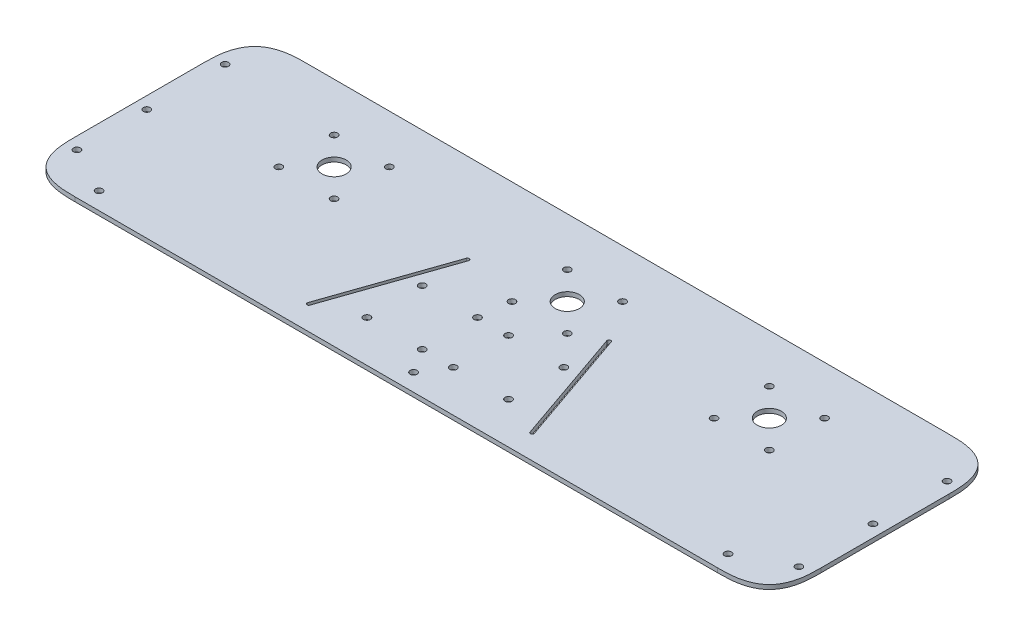
SolidWorks part; units mm, degrees
ref_plane "Front Plane" through (0, 0, 0) normal (0, 0, 1) x (1, 0, 0)
ref_plane "Top Plane" through (0, 0, 0) normal (0, 1, 0) x (1, 0, 0)
ref_plane "Right Plane" through (0, 0, 0) normal (1, 0, 0) x (0, 0, -1)
sketch "Sketch1" plane through (0, 0, 0) normal (0, 1, 0) x (1, 0, 0)
  line L1 (-103.134, 171.9149) -> (328.866, 171.9149)
  line L2 (-103.134, 171.9149) -> (-103.134, -28.0851)
  line L3 (-103.134, -28.0851) -> (328.866, -28.0851)
  line L4 (328.866, 171.9149) -> (328.866, -28.0851)
extrude "Boss-Extrude1" add sketch "Sketch1" along normal blind 2.5 contours L1 L4 L3 L2
sketch "Sketch3" plane through (0, 2.5, 0) normal (0, 1, 0) x (1, 0, 0)
  line L0 (-13.134, 71.9149) -> (-29.1359, 55.9131)
  line L1 (2.8678, 87.9167) -> (-29.1359, 87.9167)
  line L2 (2.8678, 87.9167) -> (2.8678, 55.9131)
  line L3 (2.8678, 55.9131) -> (-29.1359, 55.9131)
  line L4 (-29.1359, 87.9167) -> (-29.1359, 55.9131)
  line L5 (2.8678, 87.9167) -> (-29.1359, 55.9131) construction
  line L6 (2.8678, 55.9131) -> (-29.1359, 87.9167) construction
  line L7 (-103.134, 71.9149) -> (-13.134, 71.9149)
  line L8 (-103.134, 171.9149) -> (-103.134, -28.0851) construction
  line L9 (238.866, 71.9149) -> (238.866, 115.9149)
  line L14 (62.253, -0.3819) -> (46.2512, -16.3837)
  line L15 (238.866, 115.9149) -> (328.866, 115.9149)
  line L18 (328.866, 171.9149) -> (328.866, -28.0851) construction
  line L19 (238.866, 71.9149) -> (222.8641, 55.9131)
  line L20 (254.8678, 87.9167) -> (222.8641, 87.9167)
  line L21 (254.8678, 87.9167) -> (254.8678, 55.9131)
  line L22 (254.8678, 55.9131) -> (222.8641, 55.9131)
  line L23 (222.8641, 87.9167) -> (222.8641, 55.9131)
  line L24 (254.8678, 87.9167) -> (222.8641, 55.9131) construction
  line L25 (254.8678, 55.9131) -> (222.8641, 87.9167) construction
  line L27 (328.866, 71.9149) -> (238.866, 71.9149)
  line L28 (238.866, 115.9149) -> (238.866, 171.9149)
  line L29 (238.866, 171.9149) -> (328.866, 171.9149)
  line L30 (328.866, 115.9149) -> (328.866, 171.9149)
  line L31 (328.866, 115.9149) -> (-169.3435, 115.9149)
  line L32 (328.866, 115.9149) -> (328.866, 173.2785)
  line L33 (328.866, 173.2785) -> (-169.3435, 173.2785)
  line L34 (-169.3435, 115.9149) -> (-169.3435, 173.2785)
  line L35 (78.2549, 15.6199) -> (46.2512, 15.6199)
  line L36 (78.2549, 15.6199) -> (78.2549, -16.3837)
  line L37 (78.2549, -16.3837) -> (46.2512, -16.3837)
  line L38 (46.2512, 15.6199) -> (46.2512, -16.3837)
  line L39 (78.2549, 15.6199) -> (46.2512, -16.3837) construction
  line L40 (78.2549, -16.3837) -> (46.2512, 15.6199) construction
  circle A0 centre (-13.134, 71.9149) radius 7
  circle A1 centre (-29.1359, 55.9131) radius 2
  circle A2 centre (-29.1359, 87.9167) radius 2
  circle A3 centre (2.8678, 87.9167) radius 2
  circle A4 centre (2.8678, 55.9131) radius 2
  circle A10 centre (238.866, 71.9149) radius 7
  circle A11 centre (222.8641, 55.9131) radius 2
  circle A12 centre (222.8641, 87.9167) radius 2
  circle A13 centre (254.8678, 87.9167) radius 2
  circle A14 centre (254.8678, 55.9131) radius 2
  circle A15 centre (62.253, -0.3819) radius 7
  circle A16 centre (46.2512, -16.3837) radius 2
  circle A17 centre (46.2512, 15.6199) radius 2
  circle A18 centre (78.2549, 15.6199) radius 2
  circle A19 centre (78.2549, -16.3837) radius 2
  point P10 (328.866, 71.9149)
extrude "Cut-Extrude1" cut sketch "Sketch3" against normal blind 2.5 contours A2 | A3 | A4 | A1 | A0 | A11 | A14 | A13 | A10 | A12 | L32 L31 L34 L33
sketch "Sketch5" plane through (0, 2.5, 0) normal (0, 1, 0) x (1, 0, 0)
  line L0 (263.7413, -28.0851) -> (263.7413, -18.0851)
  line L3 (-103.134, -28.0851) -> (328.866, -28.0851) construction
  line L5 (263.7413, -18.0851) -> (328.866, -18.0851)
  line L6 (263.7413, -18.0851) -> (263.7413, -28.0851)
  line L7 (263.7413, -28.0851) -> (328.866, -28.0851)
  line L8 (328.866, -18.0851) -> (328.866, -28.0851)
  line L9 (263.7413, -18.0851) -> (-103.134, -18.0851)
  line L10 (263.7413, -18.0851) -> (263.7413, -28.0851)
  line L11 (263.7413, -28.0851) -> (-103.134, -28.0851)
  line L12 (-103.134, -18.0851) -> (-103.134, -28.0851)
  line M12 (328.866, -28.0851) -> (328.866, 115.9149)
  line M14 (-103.134, 115.9149) -> (-103.134, -28.0851)
  line M15 (-103.134, -28.0851) -> (328.866, -28.0851)
extrude "Cut-Extrude3" cut sketch "Sketch5" against normal blind 2.5 contours L0 L9 M14 M15 | L5 L0 M15 M12 region at (80.3036, 2.5, 23.0851) region at (296.3036, 2.5, 23.0851)
sketch "Sketch6" plane through (0, 2.5, 0) normal (0, 1, 0) x (1, 0, 0)
  line L0 (328.866, -18.0851) -> (-103.134, -18.0851) construction
  line L1 (112.866, -18.0851) -> (112.866, 21.9149)
  line L2 (112.866, 21.9149) -> (137.866, 21.9149)
  line L3 (112.866, 21.9149) -> (87.866, 21.9149)
  line L4 (87.866, 21.9149) -> (71.8641, 5.9131)
  line L5 (103.8678, 37.9167) -> (71.8641, 37.9167)
  line L6 (103.8678, 37.9167) -> (103.8678, 5.9131)
  line L7 (103.8678, 5.9131) -> (71.8641, 5.9131)
  line L8 (71.8641, 37.9167) -> (71.8641, 5.9131)
  line L9 (103.8678, 37.9167) -> (71.8641, 5.9131) construction
  line L10 (103.8678, 5.9131) -> (71.8641, 37.9167) construction
  line L11 (137.866, 21.9149) -> (121.8641, 5.9131)
  line L12 (153.8678, 37.9167) -> (121.8641, 37.9167)
  line L13 (153.8678, 37.9167) -> (153.8678, 5.9131)
  line L14 (153.8678, 5.9131) -> (121.8641, 5.9131)
  line L15 (121.8641, 37.9167) -> (121.8641, 5.9131)
  line L16 (153.8678, 37.9167) -> (121.8641, 5.9131) construction
  line L17 (153.8678, 5.9131) -> (121.8641, 37.9167) construction
  circle A0 centre (137.866, 21.9149) radius 16
  circle A1 centre (87.866, 21.9149) radius 16
  circle A2 centre (87.866, 21.9149) radius 7
  circle A3 centre (71.8641, 5.9131) radius 2
  circle A4 centre (71.8641, 37.9167) radius 2
  circle A5 centre (103.8678, 37.9167) radius 2
  circle A6 centre (103.8678, 5.9131) radius 2
  circle A7 centre (137.866, 21.9149) radius 7
  circle A8 centre (121.8641, 5.9131) radius 2
  circle A9 centre (121.8641, 37.9167) radius 2
  circle A10 centre (153.8678, 37.9167) radius 2
  circle A11 centre (153.8678, 5.9131) radius 2
  point P0 (112.866, -18.0851)
extrude "Cut-Extrude4" cut sketch "Sketch6" against normal blind 2.5 contours A11 | A8 | A10 | A9 | A5 | A6 | A3 | A4
sketch "Sketch8" plane through (0, 2.5, 0) normal (0, 1, 0) x (1, 0, 0)
  line L2 (153.8678, 5.9131) -> (153.8678, 90.0973)
  line L3 (153.8678, 90.0973) -> (71.8641, 90.0973)
  line L4 (71.8641, 90.0973) -> (71.8641, 5.9131)
  line L5 (153.8678, 64.0929) -> (71.8641, 64.0929)
  line L10 (177.527, -4.0851) -> (153.8678, 64.0929) construction
  line L14 (176.5823, -4.4129) -> (152.9231, 63.7651)
  line L15 (178.4718, -3.7572) -> (154.8125, 64.4208)
  line L16 (48.2049, -4.0851) -> (71.8641, 64.0929) construction
  line L17 (47.2602, -3.7572) -> (70.9194, 64.4208)
  line L18 (49.1496, -4.4129) -> (72.8089, 63.7651)
  arc A6 (176.5823, -4.4129) -> (178.4718, -3.7572) centre (177.527, -4.0851) ccw
  arc A7 (154.8125, 64.4208) -> (152.9231, 63.7651) centre (153.8678, 64.0929) ccw
  arc A8 (47.2602, -3.7572) -> (49.1496, -4.4129) centre (48.2049, -4.0851) ccw
  arc A9 (72.8089, 63.7651) -> (70.9194, 64.4208) centre (71.8641, 64.0929) ccw
  point P17 (177.527, 5.9131)
  point P18 (48.2049, 5.9131)
  point P19 (165.6974, 30.0039)
  point P22 (112.866, -4.0851)
  point P27 (60.0345, 30.0039)
extrude "Cut-Extrude5" cut sketch "Sketch8" against normal blind 2.5 contours L17 A9 L18 A8 | L15 A7 L14 A6
fillet "Fillet1" radius 30 4 edges at (-103.134, 1.25, -115.9149) (-103.134, 1.25, 18.0851) (328.866, 1.25, -115.9149) (328.866, 1.25, 18.0851) curvature continuous yes
sketch "Sketch9" plane through (0, 2.5, 0) normal (0, 1, 0) x (1, 0, 0)
  line L0 (328.866, 62.6221) -> (321.866, 62.6221)
  line L1 (328.866, 85.9149) -> (328.866, 11.9149) construction
  line L2 (321.866, 109.7214) -> (321.866, -11.8915)
  line L3 (321.866, 6.0103) -> (321.866, -11.8915)
  line L4 (321.866, 109.7214) -> (321.866, 91.8196)
  line L5 (321.866, 91.8196) -> (321.866, 109.7214)
  line L6 (-103.134, 46.4673) -> (-96.134, 46.4673)
  line L7 (-103.134, 85.9149) -> (-103.134, 11.9149) construction
  line L8 (-96.134, 46.4673) -> (-96.134, 109.7214)
  line L9 (-96.134, 109.7214) -> (-96.134, -11.8916)
  line L10 (-96.134, -11.8916) -> (-96.134, 6.0103)
  line L11 (-96.134, 109.7214) -> (-96.134, 97.3154)
  line L12 (-96.134, 109.7214) -> (-96.134, 91.8196)
  circle A0 centre (321.866, 6.0103) radius 2
  circle A1 centre (321.866, 48.9149) radius 2
  circle A2 centre (321.866, 91.8196) radius 2
  circle A3 centre (-96.134, 46.4673) radius 2
  circle A4 centre (-96.134, 91.8196) radius 2
  circle A5 centre (-96.134, 6.0103) radius 2
  spline S0 degree 2 poles (328.866, 85.9149) (328.866, 87.9765) (328.8467, 89.0459) (328.8162, 90.7467) (328.7231, 92.1742) (328.5043, 95.5283) (327.8783, 98.3317) (326.3274, 105.2776) (322.2688, 109.3319) (318.2198, 113.3765) (311.2895, 114.9258) (308.4764, 115.5546) (305.1048, 115.7733) (303.6844, 115.8655) (301.9893, 115.8958) (300.9233, 115.9149) (298.866, 115.9149) knots 0 0 0 0.0625 0.0625 0.125 0.125 0.25 0.25 0.5 0.5 0.75 0.75 0.875 0.875 0.9375 0.9375 1 1 1 construction
  spline S1 degree 2 poles (298.866, -18.0851) (300.9275, -18.0851) (301.997, -18.0659) (303.6978, -18.0353) (305.1253, -17.9422) (308.4794, -17.7234) (311.2827, -17.0975) (318.2287, -15.5466) (322.283, -11.4879) (326.3276, -7.4389) (327.8768, -0.5086) (328.5057, 2.3045) (328.7244, 5.6761) (328.8165, 7.0965) (328.8469, 8.7916) (328.866, 9.8575) (328.866, 11.9149) knots 0 0 0 0.0625 0.0625 0.125 0.125 0.25 0.25 0.5 0.5 0.75 0.75 0.875 0.875 0.9375 0.9375 1 1 1 construction
  spline S2 degree 2 poles (-73.134, 115.9149) (-75.1956, 115.9149) (-76.2651, 115.8957) (-77.9658, 115.8651) (-79.3933, 115.772) (-82.7474, 115.5532) (-85.5508, 114.9273) (-92.4967, 113.3764) (-96.551, 109.3177) (-100.5957, 105.2687) (-102.1449, 98.3384) (-102.7737, 95.5254) (-102.9924, 92.1538) (-103.0846, 90.7333) (-103.1149, 89.0383) (-103.134, 87.9723) (-103.134, 85.9149) knots 0 0 0 0.0625 0.0625 0.125 0.125 0.25 0.25 0.5 0.5 0.75 0.75 0.875 0.875 0.9375 0.9375 1 1 1 construction
  spline S3 degree 2 poles (-103.134, 11.9149) (-103.134, 9.8534) (-103.1148, 8.7839) (-103.0842, 7.0831) (-102.9911, 5.6556) (-102.7723, 2.3015) (-102.1464, -0.5019) (-100.5955, -7.4478) (-96.5368, -11.5021) (-92.4879, -15.5467) (-85.5575, -17.0959) (-82.7445, -17.7248) (-79.3729, -17.9435) (-77.9525, -18.0356) (-76.2574, -18.066) (-75.1914, -18.0851) (-73.134, -18.0851) knots 0 0 0 0.0625 0.0625 0.125 0.125 0.25 0.25 0.5 0.5 0.75 0.75 0.875 0.875 0.9375 0.9375 1 1 1 construction
extrude "Cut-Extrude6" cut sketch "Sketch9" against normal blind 2.5 contours A0 | A1 | A2 | A5 | A3 | A4
sketch "Sketch10" plane through (0, 2.5, 0) normal (0, 1, 0) x (1, 0, 0)
  line L0 (232.1904, -18.0851) -> (232.1904, -8.0851)
  line L1 (298.866, -18.0851) -> (-73.134, -18.0851) construction
  line L2 (324.9418, -8.0851) -> (-99.2097, -8.0851)
  line L3 (324.9418, -8.0851) -> (232.1904, -8.0851)
  line L4 (324.9418, -8.0851) -> (232.1904, -8.0851)
  line L5 (324.9418, -8.0851) -> (232.1904, -8.0851)
  line L6 (324.9418, -8.0851) -> (294.9418, -8.0851)
  line L7 (-99.2097, -8.0851) -> (-78.7572, -8.0851)
  line L8 (-99.2097, -8.0851) -> (-69.2097, -8.0851)
  circle A0 centre (112.866, -8.0851) radius 2
  circle A3 centre (294.9418, -8.0851) radius 2
  circle A4 centre (-69.2097, -8.0851) radius 2
  spline S0 degree 2 poles (298.866, -18.0851) (300.9275, -18.0851) (301.997, -18.0659) (303.6978, -18.0353) (305.1253, -17.9422) (308.4794, -17.7234) (311.2827, -17.0975) (318.2287, -15.5466) (322.283, -11.4879) (326.3276, -7.4389) (327.8768, -0.5086) (328.5057, 2.3045) (328.7244, 5.6761) (328.8165, 7.0965) (328.8469, 8.7916) (328.866, 9.8575) (328.866, 11.9149) knots 0 0 0 0.0625 0.0625 0.125 0.125 0.25 0.25 0.5 0.5 0.75 0.75 0.875 0.875 0.9375 0.9375 1 1 1 construction
  spline S1 degree 2 poles (-103.134, 11.9149) (-103.134, 9.8534) (-103.1148, 8.7839) (-103.0842, 7.0831) (-102.9911, 5.6556) (-102.7723, 2.3015) (-102.1464, -0.5019) (-100.5955, -7.4478) (-96.5368, -11.5021) (-92.4879, -15.5467) (-85.5575, -17.0959) (-82.7445, -17.7248) (-79.3729, -17.9435) (-77.9525, -18.0356) (-76.2574, -18.066) (-75.1914, -18.0851) (-73.134, -18.0851) knots 0 0 0 0.0625 0.0625 0.125 0.125 0.25 0.25 0.5 0.5 0.75 0.75 0.875 0.875 0.9375 0.9375 1 1 1 construction
extrude "Cut-Extrude7" cut sketch "Sketch10" against normal blind 2.5 contours A4 | A0 | A3
sketch "Sketch11" plane through (0, 2.5, 0) normal (0, 1, 0) x (1, 0, 0)
  line L0 (71.8641, 37.9167) -> (71.8641, 115.9149)
  line L1 (298.866, 115.9149) -> (-73.134, 115.9149) construction
  line L2 (153.8678, 37.9167) -> (153.8678, 115.9149)
  line L3 (-13.134, 71.9149) -> (170.9876, 71.9149)
  line L4 (121.8641, 37.9167) -> (121.8641, 95.7488)
  line L5 (121.8641, 71.9149) -> (105.8623, 55.9131)
  line L6 (137.866, 87.9167) -> (105.8623, 87.9167)
  line L7 (137.866, 87.9167) -> (137.866, 55.9131)
  line L8 (137.866, 55.9131) -> (105.8623, 55.9131)
  line L9 (105.8623, 87.9167) -> (105.8623, 55.9131)
  line L10 (137.866, 87.9167) -> (105.8623, 55.9131) construction
  line L11 (137.866, 55.9131) -> (105.8623, 87.9167) construction
  circle A1 centre (121.8641, 71.9149) radius 7
  circle A3 centre (105.8623, 55.9131) radius 2
  circle A4 centre (105.8623, 87.9167) radius 2
  circle A5 centre (137.866, 87.9167) radius 2
  circle A6 centre (137.866, 55.9131) radius 2
  point P8 (121.8641, 71.9149)
extrude "Cut-Extrude8" cut sketch "Sketch11" against normal blind 10 contours A6 | A3 | A4 | A5 | A1
